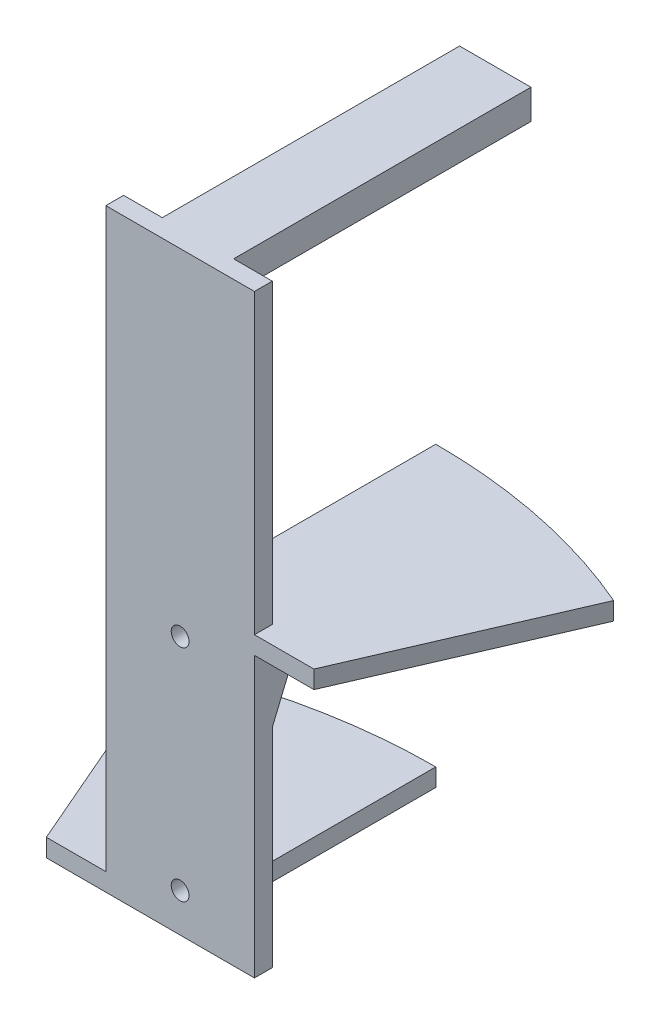
SolidWorks part; units mm, degrees
ref_plane "前视基准面" through (0, 0, 0) normal (0, 0, 1) x (1, 0, 0)
ref_plane "上视基准面" through (0, 0, 0) normal (0, 1, 0) x (1, 0, 0)
ref_plane "右视基准面" through (0, 0, 0) normal (1, 0, 0) x (0, 0, -1)
sketch "草图1" plane through (0, 0, 0) normal (0, 0, 1) x (1, 0, 0)
  line L0 (19.9568, 0) -> (-30.4572, 0) construction
  line L1 (12.5, 25) -> (-12.5, 25)
  line L2 (12.5, 25) -> (12.5, -25)
  line L3 (12.5, -25) -> (-12.5, -25)
  line L4 (-12.5, 25) -> (-12.5, -25)
  line L5 (12.5, 25) -> (-12.5, -25) construction
  line L6 (12.5, -25) -> (-12.5, 25) construction
  circle A0 centre (0, 18.5) radius 1.5
  circle A1 centre (0, -18.5) radius 1.5
  point P0 (0, 0)
  dimension "D1" = 3
  dimension "D2" = 18.5
  dimension "D3" = 25
  dimension "D4" = 50
extrude "凸台-拉伸1" add sketch "草图1" along normal blind 3
sketch "草图4" plane through (0, 0, 0) normal (0, 1, 0) x (1, 0, 0)
  line L0 (0, 7.9632) -> (0, -20.5603) construction
  line L1 (12.5, -3) -> (-12.5, -3) construction
  line L2 (-22.5, -3) -> (22.5, -3)
  line L3 (-22.5, -3) -> (-37.7256, 32.1882)
  line L4 (22.5, -3) -> (37.7256, 32.1882)
  arc A0 (37.7256, 32.1882) -> (-37.7256, 32.1882) centre (0, -55) ccw
  point P3 (0, -55)
  dimension "D2" = 190
  dimension "D1" = 52
  dimension "D3" = 10
extrude "凸台-拉伸2" add sketch "草图4" along normal blind 3 from offset 22
mirror "镜向1" about plane through (0, 0, 0) normal (0, 1, 0) of "凸台-拉伸2"
sketch "草图5" plane through (0, -25, 0) normal (0, -1, 0) x (1, 0, 0)
  line L0 (12.5, 0) -> (12.5, 3) construction
  line L1 (0, 0) -> (12.5, 0)
  line L2 (0, 0) -> (0, -43.5485)
  line L3 (0, -43.5485) -> (39.0275, -43.5485)
  line L4 (39.0275, 3) -> (39.0275, -43.5485)
  line L5 (12.5, 0) -> (12.5, 3)
  line L6 (12.5, 3) -> (39.0275, 3)
extrude "切除-拉伸1" cut sketch "草图5" against normal blind 3
sketch "草图6" plane through (0, 25, 0) normal (0, 1, 0) x (1, 0, 0)
  line L0 (-12.5, 0) -> (-12.5, -3) construction
  line L1 (0, 0) -> (-12.5, 0)
  line L2 (0, 0) -> (0, 42.9158)
  line L3 (0, 42.9158) -> (-39.0638, 42.9158)
  line L4 (-39.0638, -3) -> (-39.0638, 42.9158)
  line L5 (-12.5, 0) -> (-12.5, -3)
  line L6 (-12.5, -3) -> (-39.0638, -3)
extrude "切除-拉伸2" cut sketch "草图6" against normal blind 3
sketch "草图7" plane through (-12.5, 0, 0) normal (-1, 0, 0) x (0, 0, 1)
  line L0 (-5, -22) -> (0, -10)
  line L1 (-32.1882, -22) -> (3, -22) construction
  line L2 (0, 25) -> (0, -22) construction
  dimension "D1" = 5
  dimension "D2" = 12
rib "筋1" sketch "草图7" sketch "草图7" thickness 3 extrusion direction parallel to sketch draft on no parameters "D1"=3
ref_axis "基准轴1" through (0, 0, -26.4) along (0, 0, 1)
pattern_circular "阵列(圆周)1" count 2 every 180 about axis through (0, 0, -26.4) along (0, 0, 1) of "筋1"
sketch "草图8" plane through (0, 25, 0) normal (0, 1, 0) x (1, 0, 0)
  line L0 (12.5, 0) -> (-12.5, 0)
  line L1 (-12.5, -3) -> (-12.5, 5) construction
  line L2 (-12.5, -3) -> (-12.5, 0) construction
  line L3 (-12.5, 0) -> (-12.5, -3)
  line L4 (-12.5, -3) -> (12.5, -3)
  line L5 (0, 26.4) -> (0, -4.4) construction
  line L6 (22.5, -3) -> (-12.5, -3) construction
  line L7 (0, 3.2291) -> (0, -5.9879) construction
  line L8 (12.5, 0) -> (12.5, -3)
  point P18 (0, -3)
  point P19 (0, 0)
extrude "凸台-拉伸3" add sketch "草图8" along normal blind 50
sketch "草图9" plane through (0, 0, 0) normal (0, 0, -1) x (-1, 0, 0)
  line L0 (0, 49.0215) -> (0, 36.9266) construction
  line L1 (6, 75) -> (-6, 75)
  line L2 (-12.5, 75) -> (12.5, 75) construction
  line L3 (-6, 75) -> (-6, 70)
  line L4 (-6, 70) -> (6, 70)
  line L5 (6, 75) -> (6, 70)
  point P10 (0, 70)
  point P11 (0, 75)
  dimension "D1" = 5
  dimension "D2" = 6
extrude "凸台-拉伸4" add sketch "草图9" along normal blind 50
sketch "草图10" plane through (0, 0, 0) normal (0, 0, -1) x (-1, 0, 0)
  line L0 (-12.5, 25) -> (0, 25) construction
  line L1 (-6, 70) -> (-3, 70)
  line L2 (-6, 70) -> (-6, 25)
  line L3 (-6, 25) -> (-3, 25)
  line L4 (-3, 70) -> (-3, 25)
  line L5 (0, 70) -> (0, 17) construction
  line L6 (3, 70) -> (3, 25)
  line L7 (6, 25) -> (3, 25)
  line L8 (6, 70) -> (6, 25)
  line L9 (6, 70) -> (3, 70)
  circle A0 centre (0, 18.5) radius 1.5 construction
  dimension "D1" = 3
extrude "凸台-拉伸5" add sketch "草图10" along normal blind 3
